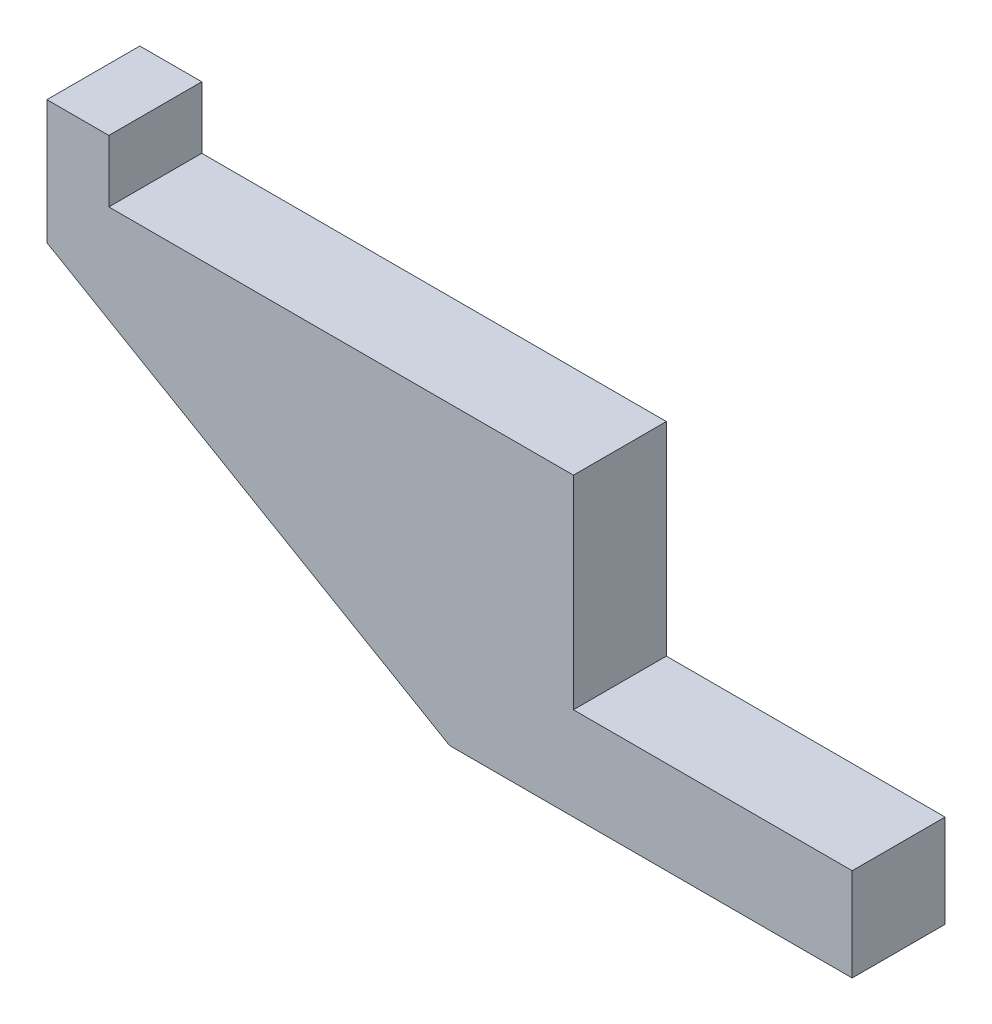
SolidWorks part; units mm, degrees
ref_plane "Front Plane" through (0, 0, 0) normal (0, 0, 1) x (1, 0, 0)
ref_plane "Top Plane" through (0, 0, 0) normal (0, 1, 0) x (1, 0, 0)
ref_plane "Right Plane" through (0, 0, 0) normal (1, 0, 0) x (0, 0, -1)
sketch "Sketch1" plane through (0, 0, 0) normal (0, 0, 1) x (1, 0, 0)
  line L0 (-451.872, -4.2328) -> (-451.872, -19.2328)
  line L6 (-581.872, 18.5672) -> (-581.872, 38.5672)
  line L7 (-581.872, 38.5672) -> (-571.872, 38.5672)
  line L8 (-571.872, 38.5672) -> (-571.872, 28.5672)
  line L9 (-571.872, 28.5672) -> (-496.872, 28.5672)
  line L10 (-496.872, 28.5672) -> (-496.872, -4.2328)
  line L11 (-496.872, -4.2328) -> (-451.872, -4.2328)
  line L13 (-451.872, -19.2328) -> (-516.872, -19.2328)
  line L14 (-516.872, -19.2328) -> (-581.872, 18.5672)
  dimension "D1" = 75
  dimension "D2" = 45
  dimension "D3" = 10
  dimension "D4" = 32.8
  dimension "D5" = 20
  dimension "D6" = 15
  dimension "D7" = 65
  dimension "D8" = 10
extrude "Boss-Extrude1" add sketch "Sketch1" along normal blind 7.5 and the other way blind 7.5 contours L14 L6 L10 | L6 region at (-521.1648, 6.247, 0)
